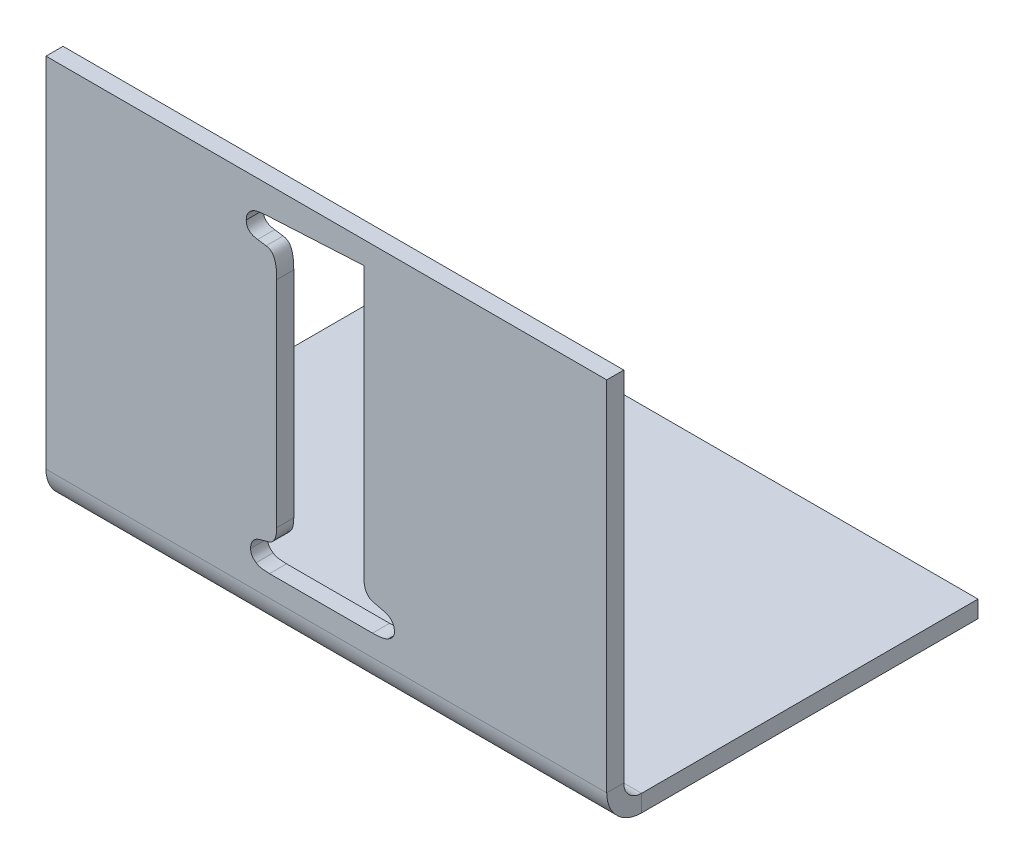
SolidWorks part; units mm, degrees
note: The reader was unsure of these and kept them because the rebuilt part matched: flange length of "Edge-Flange1".
material "16 Ga. SHEET METAL"
ref_plane "Front Plane" through (0, 0, 0) normal (0, 0, 1) x (1, 0, 0)
ref_plane "Top Plane" through (0, 0, 0) normal (0, 1, 0) x (1, 0, 0)
ref_plane "Right Plane" through (0, 0, 0) normal (1, 0, 0) x (0, 0, -1)
sketch "Sketch1" plane through (0, 0, 0) normal (0, 1, 0) x (1, 0, 0)
  line L1 (-25, 0) -> (25, 0)
  line L2 (-25, 0) -> (-25, 30)
  line L3 (-25, 30) -> (25, 30)
  line L4 (25, 0) -> (25, 30)
  dimension "D1" = 30
  dimension "D2" = 50
base flange "Base-Flange1" sketch "Sketch1" thickness 1.5189 reverse thickness direction yes parameters "D1"=1.5875
edge flange "Edge-Flange1" sketch "Sketch8" flange angle 90 flange length 35 flange position bend outside bend radius 1.5875 thickness 1.5189 relief rectangular parameters "D6"=10
sketch "Sketch8" plane through (0, 1.5189, 0) normal (0, 0, 1) x (1, 0, 0)
  line L0 (-25, 0) -> (25, 0) construction
  line L1 (-25, 0) -> (25, 0)
  line L2 (-25, 0) -> (-25, 33.4811)
  line L3 (-25, 33.4811) -> (25, 33.4811)
  line L4 (25, 33.4811) -> (25, 0)
bend "EdgeBend1" bend radius 1.5875 bend angle 90 parameters "D5"=1
hole_wizard "M8 Clearance Hole1" positions "Sketch9" profile "Sketch10" hole size "M8" standard "Peddi DIN" end condition through all
sketch "Sketch9" plane through (0, 1.5189, 0) normal (0, 1, 0) x (1, 0, 0)
  line L0 (25, -3.1064) -> (-25, -3.1064) construction
  line L1 (-25, 30) -> (-25, 0) construction
  point P0 (-13, 21.8936)
  dimension "D1" = 25
  dimension "D2" = 12
sketch "Sketch10" plane through (-13, 1.5189, -21.8936) normal (1, 0, 0) x (0, 0, 1)
  line L0 (0, 0) -> (0, 1.5189)
  line L1 (0, 1.5189) -> (4.5, 1.5189)
  line L2 (4.5, 1.5189) -> (4.5, 0)
  line L5 (4.5, 0) -> (0, 0)
  line L11 (0, -6.35) -> (0, 107.95) construction
  dimension "Thru Hole Dia." = 9
  dimension "Thru Hole Depth" = 1.5189
sketch "Sketch11" plane through (0, 0, 3.1064) normal (0, 0, 1) x (1, 0, 0)
  line L0 (-25, 0) -> (25, 0) construction
  text T0 "1" font "Stencil" height 28
  dimension "D1" = 5
extrude "Cut-Extrude1" cut sketch "Sketch11" against normal through all
other "Freeze***"
sketch "Bend-Lines1" [suppressed] plane through (0, 0, 0) normal (0, 1, 0) x (1, 0, 0)
sketch "Bounding-Box1" [suppressed] plane through (0, 0, 0) normal (0, 1, 0) x (1, 0, 0)
sheet metal parameters "Sheet-Metal1" thickness 1.5189 parameters "D1"=1.5875
flat pattern "Flat-Pattern1" [suppressed]
sketch "Bend-Lines2" plane through (0, 0, 0) normal (0, 1, 0) x (1, 0, 0)
sketch "Bounding-Box2" [suppressed] plane through (0, 0, 0) normal (0, 1, 0) x (1, 0, 0)
sheet metal parameters "Sheet-Metal2" thickness 1.5189 parameters "D1"=1.5875
flat pattern "Flat-Pattern1" [suppressed]
sketch "Bend-Lines2" plane through (0, 0, 0) normal (0, 1, 0) x (1, 0, 0)
sketch "Bounding-Box2" [suppressed] plane through (0, 0, 0) normal (0, 1, 0) x (1, 0, 0)
bend of the flat pattern "Flatten-<EdgeBend1>1"
sheet metal parameters "Sheet-Metal3" thickness 1.5189 parameters "D1"=1.5875
flat pattern "Flat-Pattern1" [suppressed]
sketch "Bend-Lines2" plane through (0, 0, 0) normal (0, 1, 0) x (1, 0, 0)
sketch "Bounding-Box2" [suppressed] plane through (0, 0, 0) normal (0, 1, 0) x (1, 0, 0)
bend of the flat pattern "Flatten-<EdgeBend1>1"
sheet metal parameters "Sheet-Metal4" thickness 1.5189 parameters "D1"=1.5875
flat pattern "Flat-Pattern1"
sketch "Bend-Lines2" plane through (0, 0, 0) normal (0, -1, 0) x (-1, 0, 0)
  line L0 (-25, -1.724) -> (25, -1.724) construction
  line L1 (-25, -1.724) -> (25, -1.724) construction
sketch3d "Bounding-Box2" [suppressed]
  line L0 (25, -35.3416, 0) -> (25, 30, 0) construction
  line L1 (-25, -35.3416, 0) -> (-25, 30, 0) construction
  line L2 (25, -35.3416, 0) -> (-25, -35.3416, 0) construction
  line L3 (25, 30, 0) -> (-25, 30, 0) construction
bend of the flat pattern "Flatten-<EdgeBend1>1"
